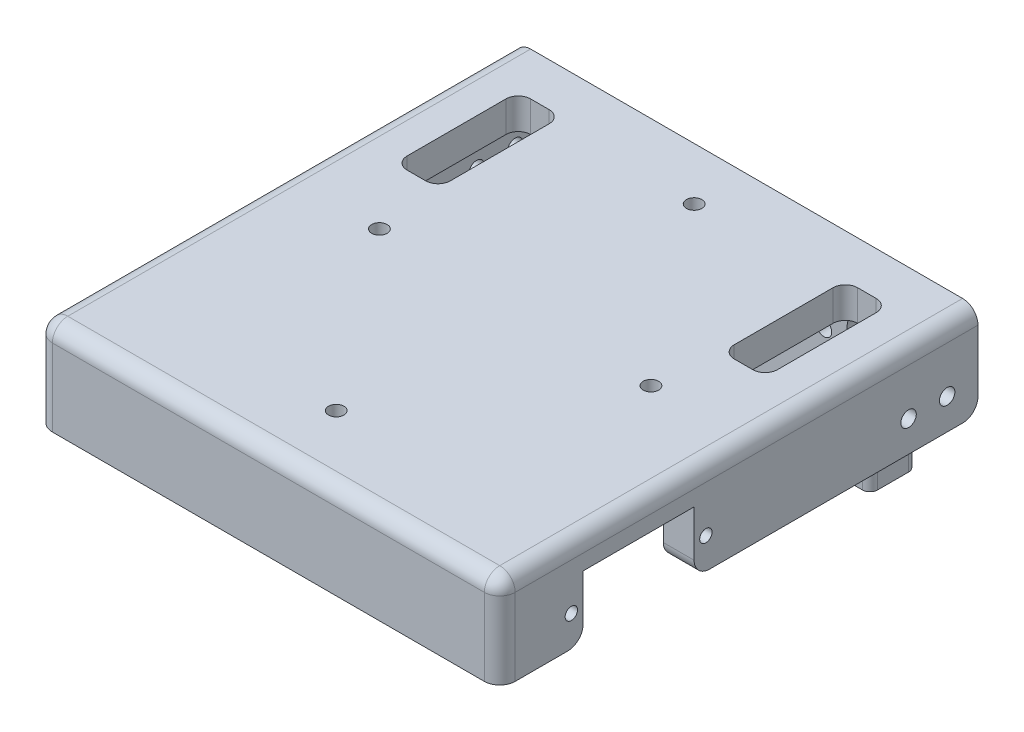
SolidWorks part; units mm, degrees
ref_plane "Front Plane" through (0, 0, 0) normal (0, 0, 1) x (1, 0, 0)
ref_plane "Top Plane" through (0, 0, 0) normal (0, 1, 0) x (1, 0, 0)
ref_plane "Right Plane" through (0, 0, 0) normal (1, 0, 0) x (0, 0, -1)
sketch "Sketch1" plane through (0, 0, 0) normal (0, 1, 0) x (1, 0, 0)
  line L1 (-47.625, -47.625) -> (47.625, -47.625)
  line L2 (-47.625, -47.625) -> (-47.625, 47.625)
  line L3 (-47.625, 47.625) -> (47.625, 47.625)
  line L4 (47.625, -47.625) -> (47.625, 47.625)
  line L5 (-47.625, -47.625) -> (47.625, 47.625) construction
  line L6 (-47.625, 47.625) -> (47.625, -47.625) construction
  point P0 (0, 0)
  dimension "D1" = 95.25
  dimension "D2" = 95.25
extrude "Boss-Extrude1" add sketch "Sketch1" along normal blind 6.35
sketch "Sketch4" plane through (0, 0, 0) normal (0, -1, 0) x (-1, 0, 0)
  line L0 (-47.625, 0) -> (-50047.625, 0) construction
  line L1 (-47.625, -47.625) -> (-47.625, 47.625) construction
  line L2 (47.625, 47.625) -> (47.625, -47.625) construction
  line L3 (-41.275, -47.625) -> (-47.625, -47.625)
  line L4 (-41.275, -47.625) -> (-41.275, 47.625)
  line L5 (-41.275, 47.625) -> (-47.625, 47.625)
  line L6 (-47.625, -47.625) -> (-47.625, 47.625)
  line L7 (-41.275, -47.625) -> (-47.625, 47.625) construction
  line L8 (-41.275, 47.625) -> (-47.625, -47.625) construction
  line L9 (41.275, -47.625) -> (47.625, -47.625)
  line L10 (41.275, -47.625) -> (41.275, 47.625)
  line L11 (41.275, 47.625) -> (47.625, 47.625)
  line L12 (47.625, -47.625) -> (47.625, 47.625)
  line L13 (41.275, -47.625) -> (47.625, 47.625) construction
  line L14 (41.275, 47.625) -> (47.625, -47.625) construction
  line L15 (47.625, -47.625) -> (-47.625, -47.625) construction
  point P4 (-47.625, 0)
  point P5 (-44.45, 0)
  point P10 (44.45, 0)
  dimension "D1" = 6.35
extrude "Boss-Extrude2" add sketch "Sketch4" along normal blind 12.7
sketch "Sketch5" plane through (-41.275, 0, 0) normal (1, 0, 0) x (0, 0, -1)
  line L0 (-22.225, -1.016) -> (-22.225, -11.684) construction
  line L1 (47.625, 0) -> (-47.625, 0) construction
  line L3 (-47.625, 6.35) -> (-47.625, -12.7) construction
  line L4 (-33.655, -12.7) -> (-10.795, -12.7)
  line L5 (-33.655, -12.7) -> (-33.655, 0)
  line L6 (-33.655, 0) -> (-10.795, 0)
  line L7 (-10.795, -12.7) -> (-10.795, 0)
  line L8 (-33.655, -12.7) -> (-10.795, 0) construction
  line L9 (-33.655, 0) -> (-10.795, -12.7) construction
  line L10 (47.625, -12.7) -> (-47.625, -12.7) construction
  point P6 (-22.225, -6.35)
  dimension "D1" = 22.86
  dimension "D2" = 25.4
extrude "Cut-Extrude1" cut sketch "Sketch5" against normal through all both and the other way through all
sketch "Sketch6" plane through (-47.625, 0, 0) normal (-1, 0, 0) x (0, 0, 1)
  line L0 (34.29, -6.35) -> (50034.29, -6.35) construction
  line L1 (33.655, 0) -> (33.655, -12.7) construction
  line L3 (10.795, 0) -> (33.655, 0) construction
  circle A0 centre (36.068, -6.35) radius 1.27
  circle A1 centre (8.382, -6.35) radius 1.27
  point P4 (33.655, -6.35)
  point P11 (22.225, 0)
  dimension "D3" = 2.54
  dimension "D1" = 27.686
  dimension "D2" = 13.843
extrude "Cut-Extrude2" cut sketch "Sketch6" against normal through all
sketch "Sketch7" plane through (0, 0, 0) normal (0, -1, 0) x (1, 0, 0)
  line L0 (0, 0) -> (50000, 0) construction
  line L1 (0, -36.83) -> (0, 36.83) construction
  circle A0 centre (27.94, 0) radius 1.5875
  circle A1 centre (-27.94, 0) radius 1.5875
  circle A2 centre (0, 36.83) radius 1.5875
  circle A3 centre (0, -36.83) radius 1.5875
  point P10 (0, 0)
  dimension "D1" = 55.88
  dimension "D3" = 3.175
  dimension "D2" = 27.94
  dimension "D4" = 73.66
extrude "Cut-Extrude3" cut sketch "Sketch7" against normal through all
sketch "Sketch8" plane through (-41.275, 0, 0) normal (1, 0, 0) x (0, 0, -1)
  line L0 (47.625, -6.35) -> (50047.625, -6.35) construction
  line L1 (47.625, -12.7) -> (47.625, 0) construction
  circle A0 centre (41.275, -6.35) radius 1.5875
  circle A1 centre (33.3375, -6.35) radius 1.5875
  point P4 (47.625, -6.35)
  dimension "D1" = 3.175
  dimension "D2" = 6.35
  dimension "D3" = 7.9375
extrude "Cut-Extrude4" cut sketch "Sketch8" against normal through all both and the other way through all
sketch "Sketch9" plane through (0, 0, 47.625) normal (0, 0, 1) x (1, 0, 0)
  line L1 (-47.625, 6.35) -> (47.625, 6.35)
  line L2 (-47.625, 6.35) -> (-47.625, -12.7)
  line L3 (-47.625, -12.7) -> (47.625, -12.7)
  line L4 (47.625, 6.35) -> (47.625, -12.7)
extrude "Boss-Extrude3" add sketch "Sketch9" along normal blind 3.175
sketch "Sketch10" plane through (0, 0, 0) normal (0, -1, 0) x (1, 0, 0)
  line L0 (-33.655, -47.625) -> (-33.655, 47.625) construction
  line L1 (41.275, -47.625) -> (-41.275, -47.625) construction
  line L2 (-41.275, 47.625) -> (41.275, 47.625) construction
  line L3 (33.655, -47.625) -> (33.655, 47.625) construction
  line L4 (33.655, 0) -> (-33.655, 0) construction
  line L6 (-31.75, -38.735) -> (-35.56, -38.735)
  line L7 (-29.21, -36.195) -> (-29.21, -15.875)
  line L8 (-31.75, -13.335) -> (-35.56, -13.335)
  line L9 (-38.1, -36.195) -> (-38.1, -15.875)
  line L10 (-29.21, -38.735) -> (-38.1, -13.335) construction
  line L11 (-29.21, -13.335) -> (-38.1, -38.735) construction
  line L12 (35.56, -38.735) -> (31.75, -38.735)
  line L13 (38.1, -36.195) -> (38.1, -15.875)
  line L14 (35.56, -13.335) -> (31.75, -13.335)
  line L15 (29.21, -36.195) -> (29.21, -15.875)
  line L16 (38.1, -38.735) -> (29.21, -13.335) construction
  line L17 (38.1, -13.335) -> (29.21, -38.735) construction
  arc A0 (31.75, -38.735) -> (29.21, -36.195) centre (31.75, -36.195) cw
  arc A1 (35.56, -38.735) -> (38.1, -36.195) centre (35.56, -36.195) ccw
  arc A2 (38.1, -15.875) -> (35.56, -13.335) centre (35.56, -15.875) ccw
  arc A3 (31.75, -13.335) -> (29.21, -15.875) centre (31.75, -15.875) ccw
  arc A4 (-35.56, -13.335) -> (-38.1, -15.875) centre (-35.56, -15.875) ccw
  arc A5 (-29.21, -15.875) -> (-31.75, -13.335) centre (-31.75, -15.875) ccw
  arc A6 (-31.75, -38.735) -> (-29.21, -36.195) centre (-31.75, -36.195) ccw
  arc A7 (-35.56, -38.735) -> (-38.1, -36.195) centre (-35.56, -36.195) cw
  point P8 (33.655, -26.035)
  point P12 (0, 0)
  point P14 (-33.655, -26.035)
  dimension "D6" = 2.54
  dimension "D1" = 67.31
  dimension "D2" = 8.89
  dimension "D3" = 8.89
  dimension "D4" = 8.89
  dimension "D5" = 25.4
extrude "Cut-Extrude5" cut sketch "Sketch10" against normal through all
sketch "Sketch11" plane through (0, 0, -47.625) normal (0, 0, -1) x (-1, 0, 0)
  line L0 (-47.625, 6.35) -> (47.625, 6.35) construction
  line L1 (-25.4, -31.75) -> (25.4, -31.75)
  line L2 (-25.4, -31.75) -> (-25.4, 6.35)
  line L3 (-25.4, 6.35) -> (25.4, 6.35)
  line L4 (25.4, -31.75) -> (25.4, 6.35)
  line L5 (-25.4, -31.75) -> (25.4, 6.35) construction
  line L6 (-25.4, 6.35) -> (25.4, -31.75) construction
  line L7 (0, -12.7) -> (0, 0) construction
  line L8 (-41.275, 0) -> (41.275, 0) construction
  point P0 (0, -12.7)
  dimension "D1" = 50.8
  dimension "D2" = 38.1
extrude "Boss-Extrude4" add sketch "Sketch11" against normal blind 4.7625
sketch "Sketch12" plane through (0, 0, -47.625) normal (0, 0, -1) x (-1, 0, 0)
  line L0 (0, 6.35) -> (0, -31.75) construction
  line L1 (-47.625, 6.35) -> (47.625, 6.35) construction
  line L2 (-25.4, -31.75) -> (25.4, -31.75) construction
  line L4 (-20.701, -25.4) -> (20.701, -25.4) construction
  line L5 (-20.701, -25.4) -> (-20.701, -8.382) construction
  line L6 (-20.701, -8.382) -> (20.701, -8.382) construction
  line L7 (20.701, -25.4) -> (20.701, -8.382) construction
  line L8 (-20.701, -25.4) -> (20.701, -8.382) construction
  line L9 (-20.701, -8.382) -> (20.701, -25.4) construction
  line L10 (-9.525, -16.891) -> (9.525, -16.891)
  line L11 (-9.525, -16.891) -> (-9.525, -1.016)
  line L12 (-9.525, -1.016) -> (9.525, -1.016)
  line L13 (9.525, -16.891) -> (9.525, -1.016)
  line L14 (-9.525, -16.891) -> (9.525, -1.016) construction
  line L15 (-9.525, -1.016) -> (9.525, -16.891) construction
  circle A0 centre (-20.701, -8.382) radius 1.5875
  circle A1 centre (-20.701, -25.4) radius 1.5875
  circle A2 centre (20.701, -8.382) radius 1.5875
  circle A3 centre (20.701, -25.4) radius 1.5875
  point P6 (0, -16.891)
  point P15 (0, -12.7)
  point P22 (0, -8.9535)
  dimension "D3" = 3.175
  dimension "D1" = 17.018
  dimension "D2" = 6.35
  dimension "D4" = 41.402
  dimension "D5" = 19.05
  dimension "D6" = 15.875
extrude "Cut-Extrude6" cut sketch "Sketch12" against normal up to next
fillet "Fillet1" radius 6.985 4 edges at (-9.525, -16.891, -45.2437) (-9.525, -1.016, -45.2437) (9.525, -1.016, -45.2437) (9.525, -16.891, -45.2437)
fillet "Fillet2" radius 6.35 2 edges at (25.4, 0, -45.2437) (-25.4, 0, -45.2437)
fillet "Fillet3" radius 3.175 6 edges at (-44.45, -12.7, 10.795) (-44.45, -12.7, 33.655) (44.45, -12.7, 33.655) (44.45, -12.7, 10.795) (44.45, -12.7, -47.625) (-44.45, -12.7, -47.625)
fillet "Fillet4" radius 3.175 7 edges at (41.275, -6.35, 47.625) (-41.275, -6.35, 47.625) (-41.275, 0, 40.64) (-41.275, 0, -18.415) (41.275, 0, -18.415) (41.275, 0, 40.64) (0, 0, 47.625)
fillet "Fillet5" radius 3.175 5 edges at (-47.625, -3.175, 50.8) (47.625, -3.175, 50.8) (47.625, 6.35, 1.5875) (-47.625, 6.35, 1.5875) (0, 6.35, 50.8)
sketch "Sketch14" plane through (0, -31.75, 0) normal (0, -1, 0) x (1, 0, 0)
  line L1 (-25.4, -47.625) -> (-34.925, -47.625)
  line L2 (-25.4, -47.625) -> (-25.4, -38.1)
  line L3 (-25.4, -38.1) -> (-34.925, -38.1)
  line L4 (-34.925, -47.625) -> (-34.925, -38.1)
  line L5 (25.4, -47.625) -> (34.925, -47.625)
  line L6 (25.4, -47.625) -> (25.4, -38.1)
  line L7 (25.4, -38.1) -> (34.925, -38.1)
  line L8 (34.925, -47.625) -> (34.925, -38.1)
  dimension "D1" = 9.525
  dimension "D2" = 9.525
extrude "Boss-Extrude5" add sketch "Sketch14" against normal blind 9.525
sketch "Sketch15" plane through (0, -22.225, 0) normal (0, 1, 0) x (1, 0, 0)
  line L0 (30.1625, 47.625) -> (30.1625, 38.1) construction
  line L1 (25.4, 47.625) -> (34.925, 47.625) construction
  line L2 (34.925, 38.1) -> (25.4, 38.1) construction
  line L3 (-30.1625, 47.625) -> (-30.1625, 38.1) construction
  line L4 (-34.925, 47.625) -> (-25.4, 47.625) construction
  line L5 (-25.4, 38.1) -> (-34.925, 38.1) construction
  circle A0 centre (-30.1625, 42.8625) radius 1.905
  circle A1 centre (30.1625, 42.8625) radius 1.905
  dimension "D1" = 3.81
extrude "Cut-Extrude7" cut sketch "Sketch15" against normal through all
fillet "Fillet7" radius 1.5875 8 edges at (34.925, -26.9875, -47.625) (-34.925, -26.9875, -47.625) (-25.4, -26.9875, -38.1) (-34.925, -26.9875, -38.1) (34.925, -26.9875, -38.1) (25.4, -26.9875, -38.1) (25.4, -26.9875, -42.8625) (-25.4, -26.9875, -42.8625)
fillet "Fillet8" radius 1.5875 2 edges at (-25.4, -22.225, -45.2437) (25.4, -22.225, -45.2437)
sketch "Sketch16" plane through (0, -31.75, 0) normal (0, -1, 0) x (1, 0, 0)
  line L8 (-33.3375, -47.625) -> (33.3375, -47.625)
  line L9 (34.925, -46.0375) -> (34.925, -39.6875)
  line L10 (33.3375, -38.1) -> (26.9875, -38.1)
  line L11 (25.4, -39.6875) -> (25.4, -41.275)
  line L12 (23.8125, -42.8625) -> (-23.8125, -42.8625)
  line L13 (-25.4, -41.275) -> (-25.4, -39.6875)
  line L14 (-26.9875, -38.1) -> (-33.3375, -38.1)
  line L15 (-34.925, -39.6875) -> (-34.925, -46.0375)
  line L16 (-33.3375, -47.625) -> (33.3375, -47.625)
  line L17 (34.925, -46.0375) -> (34.925, -39.6875)
  line L18 (33.3375, -38.1) -> (26.9875, -38.1)
  line L19 (25.4, -39.6875) -> (25.4, -41.275)
  line L20 (23.8125, -42.8625) -> (-23.8125, -42.8625)
  line L21 (-25.4, -41.275) -> (-25.4, -39.6875)
  line L22 (-26.9875, -38.1) -> (-33.3375, -38.1)
  line L23 (-34.925, -39.6875) -> (-34.925, -46.0375)
  arc A8 (33.3375, -47.625) -> (34.925, -46.0375) centre (33.3375, -46.0375) ccw
  arc A9 (34.925, -39.6875) -> (33.3375, -38.1) centre (33.3375, -39.6875) ccw
  arc A10 (26.9875, -38.1) -> (25.4, -39.6875) centre (26.9875, -39.6875) ccw
  arc A11 (23.8125, -42.8625) -> (25.4, -41.275) centre (23.8125, -41.275) ccw
  arc A12 (-25.4, -41.275) -> (-23.8125, -42.8625) centre (-23.8125, -41.275) ccw
  arc A13 (-25.4, -39.6875) -> (-26.9875, -38.1) centre (-26.9875, -39.6875) ccw
  arc A14 (-33.3375, -38.1) -> (-34.925, -39.6875) centre (-33.3375, -39.6875) ccw
  arc A15 (-34.925, -46.0375) -> (-33.3375, -47.625) centre (-33.3375, -46.0375) ccw
  arc A16 (33.3375, -47.625) -> (34.925, -46.0375) centre (33.3375, -46.0375) ccw
  arc A17 (34.925, -39.6875) -> (33.3375, -38.1) centre (33.3375, -39.6875) ccw
  arc A18 (26.9875, -38.1) -> (25.4, -39.6875) centre (26.9875, -39.6875) ccw
  arc A19 (23.8125, -42.8625) -> (25.4, -41.275) centre (23.8125, -41.275) ccw
  arc A20 (-25.4, -41.275) -> (-23.8125, -42.8625) centre (-23.8125, -41.275) ccw
  arc A21 (-25.4, -39.6875) -> (-26.9875, -38.1) centre (-26.9875, -39.6875) ccw
  arc A22 (-33.3375, -38.1) -> (-34.925, -39.6875) centre (-33.3375, -39.6875) ccw
  arc A23 (-34.925, -46.0375) -> (-33.3375, -47.625) centre (-33.3375, -46.0375) ccw
  dimension "D1" = 0
extrude "Cut-Extrude8" cut sketch "Sketch16" against normal blind 3.175
